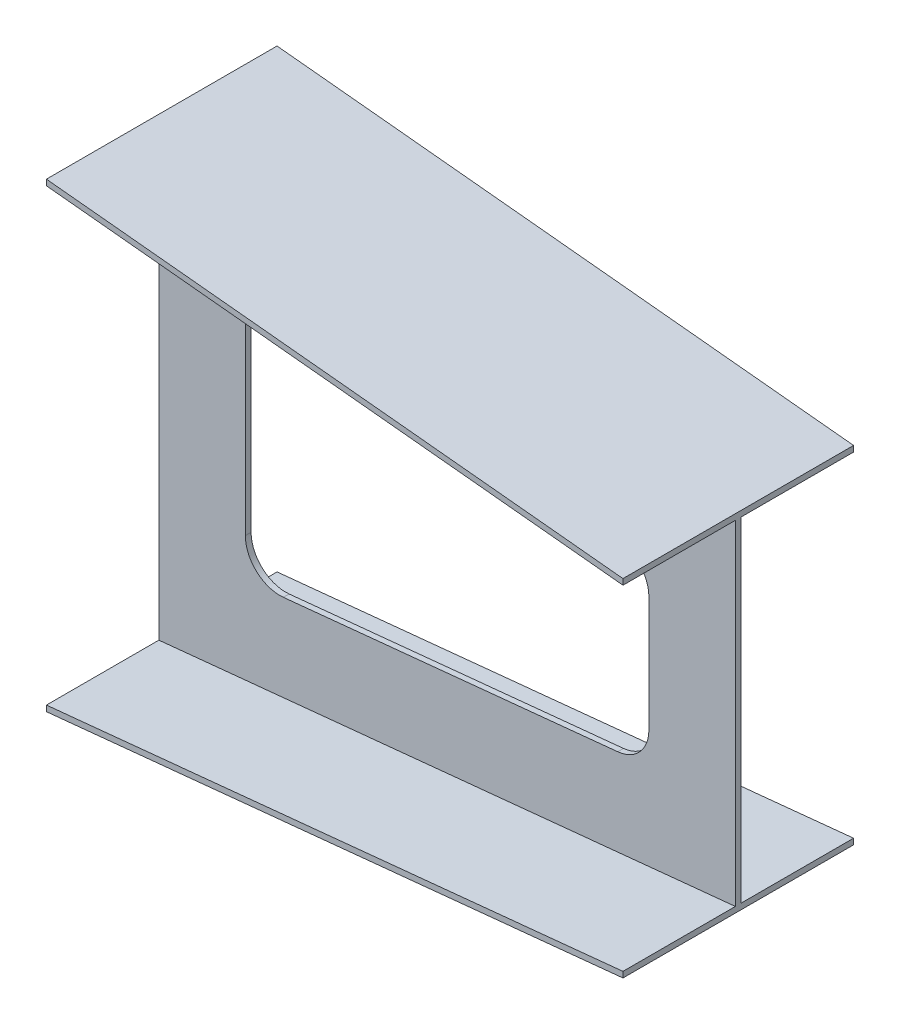
SolidWorks part; units mm, degrees
ref_plane "Front Plane" through (0, 0, 0) normal (0, 0, 1) x (1, 0, 0)
ref_plane "Top Plane" through (0, 0, 0) normal (0, 1, 0) x (1, 0, 0)
ref_plane "Right Plane" through (0, 0, 0) normal (1, 0, 0) x (0, 0, -1)
sketch "Sketch1" plane through (0, 0, 0) normal (1, 0, 0) x (0, 0, -1)
  line L1 (-205, 400) -> (195, 400)
  line L2 (-205, 400) -> (-205, 390)
  line L4 (195, 400) -> (195, 390)
  line L6 (-205, -390) -> (-205, -400)
  line L7 (-205, -400) -> (195, -400)
  line L8 (195, -390) -> (195, -400)
  line L15 (-205, -390) -> (-10, -390)
  line L16 (-5, 390) -> (-5, -590) construction
  line L18 (-205, 390) -> (-10, 390)
  line L19 (0, 0) -> (192.2403, 0) construction
  line L21 (-10, 390) -> (-10, -390)
  line L23 (0, 390) -> (0, -390)
  line L27 (0, 390) -> (195, 390)
  line L28 (0, -390) -> (195, -390)
  dimension "D1" = 400
  dimension "D2" = 10
  dimension "D3" = 800
  dimension "D4" = 10
ref_plane "Plane2" through (1000, 0, 0) normal (1, 0, 0) x (0, 0, -1)
sketch "Sketch4" plane through (1000, 0, -1000) normal (-1, 0, 0) x (0, 0, 1)
  line L1 (805, 300) -> (1205, 300)
  line L2 (805, 300) -> (805, 290)
  line L4 (1205, 300) -> (1205, 290)
  line L6 (805, -290) -> (805, -300)
  line L7 (805, -300) -> (1205, -300)
  line L8 (1205, -290) -> (1205, -300)
  line L15 (805, -290) -> (1000, -290)
  line L16 (1005, 390) -> (1005, -390) construction
  line L18 (805, 290) -> (1000, 290)
  line L19 (1010, -290) -> (1205, -290)
  line L21 (1000, 290) -> (1000, -290)
  line L23 (1010, 290) -> (1010, -290)
  line L24 (1010, 290) -> (1205, 290)
  line L26 (1010, 390) -> (1010, -390) construction
  line L27 (1000, 0) -> (820.2065, 0) construction
  dimension "D1" = 400
  dimension "D2" = 10
  dimension "D3" = 600
  dimension "D4" = 10
loft "Loft4" add profiles "Sketch1", "Sketch4" connector at (0, 390, 10) connector at (1000, 290, 10)
sketch "Sketch6" plane through (0, 0, 10) normal (0, 0, 1) x (1, 0, 0)
  line L8 (150, -224.2519) -> (850, -154.2519)
  line L9 (850, -154.2519) -> (850, 154.2519)
  line L10 (850, 154.2519) -> (150, 224.2519)
  line L11 (150, 224.2519) -> (150, -224.2519)
  line L12 (215.9702, -217.6548) -> (795.9702, -159.6548)
  line L13 (850, -99.9526) -> (850, 99.9526)
  line L14 (795.9702, 159.6548) -> (215.9702, 217.6548)
  line L15 (150, 157.9526) -> (150, -157.9526)
  arc A0 (150, -157.9526) -> (215.9702, -217.6548) centre (210, -157.9526) ccw
  arc A1 (850, 99.9526) -> (795.9702, 159.6548) centre (790, 99.9526) ccw
  arc A2 (850, -99.9526) -> (795.9702, -159.6548) centre (790, -99.9526) cw
  arc A3 (150, 157.9526) -> (215.9702, 217.6548) centre (210, 157.9526) cw
  dimension "D2" = 60
  dimension "D1" = 150
extrude "Cut-Extrude1" cut sketch "Sketch6" against normal blind 10
